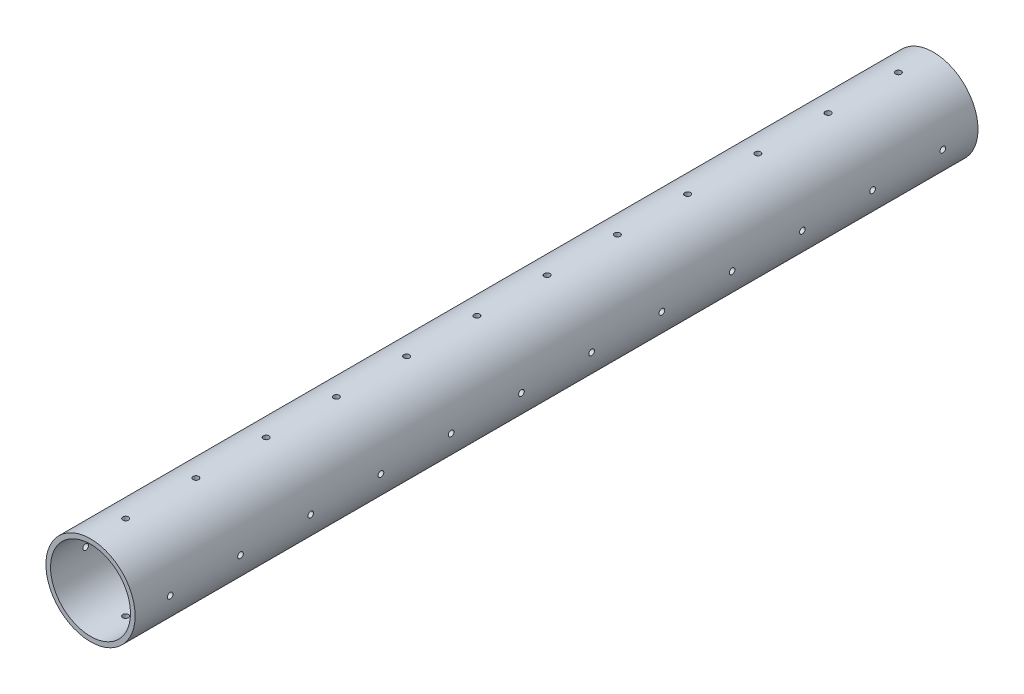
SolidWorks part; units mm, degrees
ref_plane "Front" through (0, 0, 0) normal (0, 0, 1) x (1, 0, 0)
ref_plane "Top" through (0, 0, 0) normal (0, 1, 0) x (1, 0, 0)
ref_plane "Right" through (0, 0, 0) normal (1, 0, 0) x (0, 0, -1)
ref_axis "CL" through (0, 0, -15) along (0, 0, 1)
sketch "Sketch1" plane through (0, 0, 0) normal (0, 0, 1) x (1, 0, 0)
  circle A0 centre (0, 0) radius 15.875
  circle A1 centre (0, 0) radius 14.224
  dimension "D1" = 31.75
  dimension "D2" = 28.448
extrude "Boss-Extrude1" add sketch "Sketch1" along normal blind 300
sketch "Sketch2" plane through (0, 0, 0) normal (0, 1, 0) x (1, 0, 0)
  line L0 (0, 0) -> (0, -300) construction
  line L1 (-15.875, -300) -> (15.875, -300) construction
  line L2 (14.224, 0) -> (-14.224, 0) construction
  line L3 (-15.875, -150) -> (15.875, -150) construction
  line L4 (-15.875, 0) -> (-15.875, -300) construction
  line L5 (15.875, -300) -> (15.875, 0) construction
  circle A0 centre (0, -12.5) radius 1.0125
  circle A2 centre (0, -37.5) radius 1.0125
  circle A3 centre (0, -62.5) radius 1.0125
  circle A4 centre (0, -87.5) radius 1.0125
  circle A5 centre (0, -112.5) radius 1.0125
  circle A6 centre (0, -137.5) radius 1.0125
  circle A7 centre (0, -162.5) radius 1.0125
  circle A8 centre (0, -187.5) radius 1.0125
  circle A9 centre (0, -212.5) radius 1.0125
  circle A10 centre (0, -237.5) radius 1.0125
  circle A11 centre (0, -262.5) radius 1.0125
  circle A12 centre (0, -287.5) radius 1.0125
  circle A20 centre (0, -312.5) radius 1.0125 [skipped]
  circle A21 centre (0, -337.5) radius 1.0125 [skipped]
  circle A22 centre (0, -362.5) radius 1.0125 [skipped]
  circle A23 centre (0, -387.5) radius 1.0125 [skipped]
  circle A24 centre (0, -412.5) radius 1.0125 [skipped]
  circle A25 centre (0, -437.5) radius 1.0125 [skipped]
  circle A26 centre (0, -462.5) radius 1.0125 [skipped]
  dimension "D1" = 2.025
  dimension "D2" = 12.5
  dimension "D3" = 2.025
  dimension "D4" = 25
  dimension "D5" = 18
extrude "Cut-Extrude1" cut sketch "Sketch2" against normal up to surface and the other way up to surface up to face at (15.875, 0, 300) other way up to face at (15.875, 0, 300)
sketch "Sketch3" plane through (0, 0, 0) normal (1, 0, 0) x (0, 0, -1)
  line L0 (0, 0) -> (-300, 0) construction
  line L1 (-300, 15.875) -> (-300, -15.875) construction
  line L2 (0, -14.224) -> (0, 14.224) construction
  circle A0 centre (-12.5, 0) radius 1.0125
  circle A2 centre (-37.5, 0) radius 1.0125
  circle A3 centre (-62.5, 0) radius 1.0125
  circle A4 centre (-87.5, 0) radius 1.0125
  circle A5 centre (-112.5, 0) radius 1.0125
  circle A6 centre (-137.5, 0) radius 1.0125
  circle A7 centre (-162.5, 0) radius 1.0125
  circle A8 centre (-187.5, 0) radius 1.0125
  circle A9 centre (-212.5, 0) radius 1.0125
  circle A10 centre (-237.5, 0) radius 1.0125
  circle A11 centre (-262.5, 0) radius 1.0125
  circle A12 centre (-287.5, 0) radius 1.0125
  circle A20 centre (-312.5, 0) radius 1.0125 [skipped]
  circle A21 centre (-337.5, 0) radius 1.0125 [skipped]
  circle A22 centre (-362.5, 0) radius 1.0125 [skipped]
  circle A23 centre (-387.5, 0) radius 1.0125 [skipped]
  circle A24 centre (-412.5, 0) radius 1.0125 [skipped]
  circle A25 centre (-437.5, 0) radius 1.0125 [skipped]
  circle A26 centre (-462.5, 0) radius 1.0125 [skipped]
  dimension "D2" = 2.025
  dimension "D3" = 12.5
  dimension "D5" = 2.025
  dimension "D6" = 25
  dimension "D7" = 18
extrude "Cut-Extrude2" cut sketch "Sketch3" against normal up to surface and the other way up to surface up to face at (0.2306, -15.8733, 36.5141) other way up to face at (0.2306, -15.8733, 36.5141)
ref_plane "Mid-Plane" through (0, 0, 150) normal (0, 0, 1) x (1, 0, 0)
